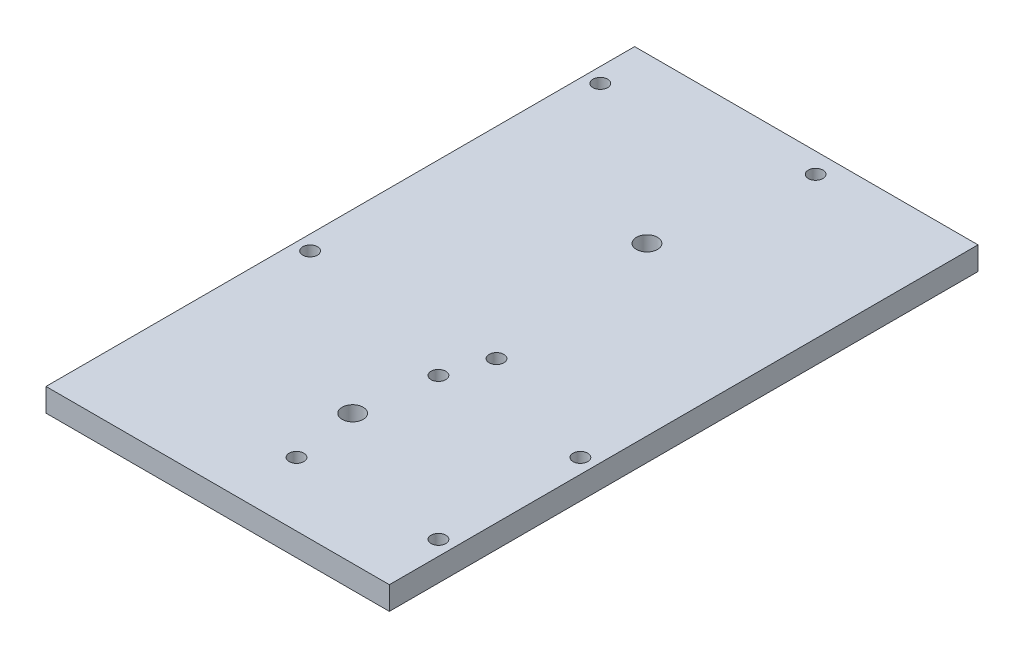
SolidWorks part; units mm, degrees
ref_plane "Front Plane" through (0, 0, 0) normal (0, 0, 1) x (1, 0, 0)
ref_plane "Top Plane" through (0, 0, 0) normal (0, 1, 0) x (1, 0, 0)
ref_plane "Right Plane" through (0, 0, 0) normal (1, 0, 0) x (0, 0, -1)
sketch "Sketch2" plane through (0, 0, 0) normal (0, 1, 0) x (1, 0, 0)
  line L1 (0, 0) -> (88.9, 0)
  line L2 (0, 0) -> (0, 152.4)
  line L3 (0, 152.4) -> (88.9, 152.4)
  line L10 (88.9, 152.4) -> (88.9, 0)
  dimension "D1" = 152.4
  dimension "D2" = 88.9
extrude "Boss-Extrude1" add sketch "Sketch2" along normal blind 5.9944 contours L3 L10 L1 L2
sketch "Sketch3" plane through (0, 5.9944, 0) normal (0, 1, 0) x (1, 0, 0)
  line L0 (0, 0) -> (0, 152.4) construction
  line L2 (0, 152.4) -> (88.9, 152.4) construction
  line L3 (85.09, 53.2638) -> (48.3362, 53.2638) construction
  line L4 (85.09, 53.2638) -> (85.09, 16.51) construction
  line L5 (85.09, 16.51) -> (48.3362, 16.51) construction
  line L6 (48.3362, 53.2638) -> (48.3362, 16.51) construction
  line L8 (0, 0) -> (88.9, 0) construction
  line L9 (0, 0) -> (88.9, 0) construction
  line L10 (88.9, 152.4) -> (88.9, 0) construction
  circle A5 centre (52.07, 147.193) radius 1.905
  circle A6 centre (3.81, 139.7) radius 1.905
  circle A7 centre (3.81, 64.5668) radius 1.905
  circle A8 centre (52.07, 64.5668) radius 1.905
  circle A9 centre (48.3362, 53.2638) radius 1.905
  circle A10 centre (85.09, 53.2638) radius 1.905
  circle A11 centre (48.3362, 16.51) radius 1.905
  circle A12 centre (85.09, 16.51) radius 1.905
  point P0 (52.07, 147.193)
  point P1 (3.81, 139.7)
  point P2 (3.81, 64.5668)
  point P3 (52.07, 64.5668)
  point P21 (85.09, 53.2638)
  point P22 (85.09, 16.51)
  point P23 (48.3362, 53.2638)
  point P24 (48.3362, 16.51)
  dimension "D4" = 3.81
  dimension "D5" = 3.81
  dimension "D6" = 3.81
  dimension "D7" = 3.81
  dimension "D9" = 3.81
  dimension "D16" = 3.81
  dimension "D17" = 3.81
  dimension "D18" = 3.81
  dimension "D19" = 3.81
  dimension "D1" = 48.26
  dimension "D2" = 82.6262
  dimension "D3" = 75.1332
  dimension "D8" = 12.7
  dimension "D10" = 36.7538
  dimension "D11" = 36.7538
  dimension "D12" = 16.51
  dimension "D13" = 3.81
  dimension "D14" = 48.3362
  dimension "D15" = 16.51
extrude "Cut-Extrude1" cut sketch "Sketch3" against normal through all both and the other way through all contours A6 | A5 | A8 | A7 | A11 | A9 | A10 | A12
sketch "Sketch4" plane through (0, 5.9944, 0) normal (0, 1, 0) x (1, 0, 0)
  line L0 (0, 0) -> (0, 152.4) construction
  line L1 (0, 0) -> (88.9, 0) construction
  circle A0 centre (45.72, 109.8713) radius 2.7305
  circle A1 centre (45.72, 33.6713) radius 2.7305
  dimension "D3" = 5.461
  dimension "D4" = 5.461
  dimension "D1" = 76.2
  dimension "D2" = 45.72
  dimension "D5" = 33.6713
extrude "Cut-Extrude2" cut sketch "Sketch4" against normal through all both
equation "\"threaded_insert_hole\"=0.1472"
equation "\"th\"=1.25249"
